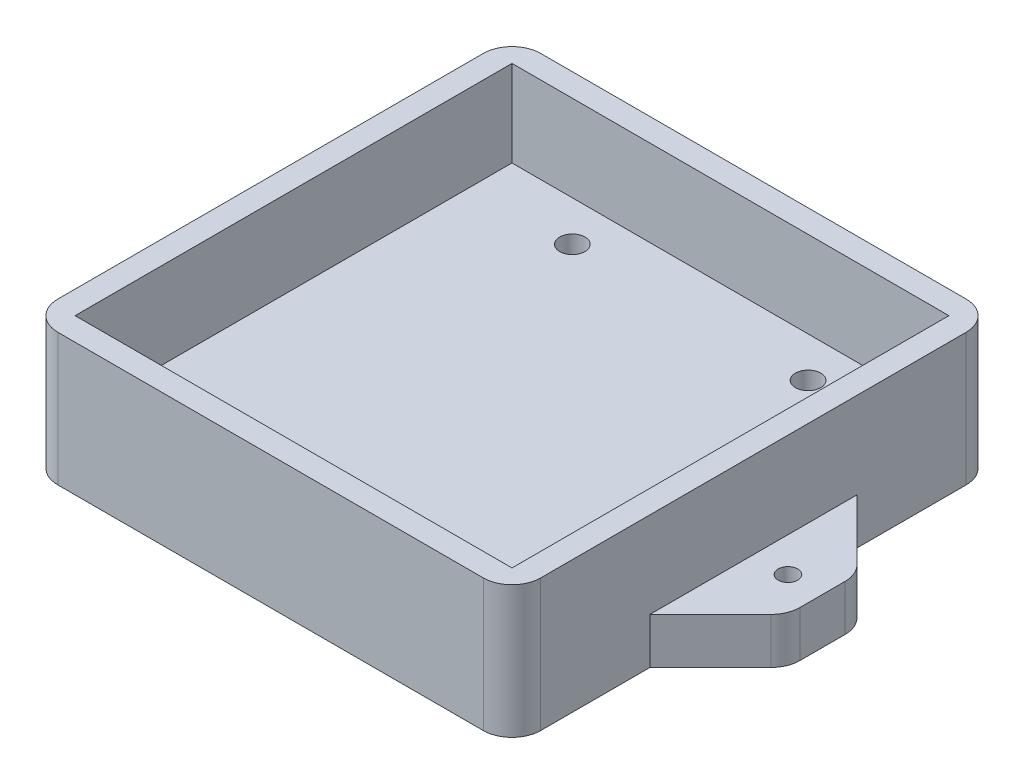
SolidWorks part; units mm, degrees
ref_plane "Front Plane" through (0, 0, 0) normal (0, 0, 1) x (1, 0, 0)
ref_plane "Top Plane" through (0, 0, 0) normal (0, 1, 0) x (1, 0, 0)
ref_plane "Right Plane" through (0, 0, 0) normal (1, 0, 0) x (0, 0, -1)
sketch "Sketch1" plane through (0, 0, 0) normal (0, 1, 0) x (1, 0, 0)
  line L0 (-42, 42) -> (-42, -42)
  line L1 (-20.5, 31) -> (20.5, 31) construction
  line L2 (-20.5, 31) -> (-20.5, -31) construction
  line L3 (-20.5, -31) -> (20.5, -31) construction
  line L4 (20.5, 31) -> (20.5, -31) construction
  line L5 (38, 38) -> (-38, 38)
  line L6 (38, 38) -> (38, -38)
  line L7 (38, -38) -> (-38, -38)
  line L8 (-38, 38) -> (-38, -38)
  line L9 (38, 38) -> (-38, -38) construction
  line L10 (38, -38) -> (-38, 38) construction
  line L11 (42, -42) -> (-42, -42)
  line L12 (42, 42) -> (42, -42)
  line L13 (42, 42) -> (-42, 42)
  line L14 (-54, 6) -> (-42, 18)
  line L15 (-42, 6) -> (-54, 6)
  line L16 (-42, 6) -> (-42, -6)
  line L17 (-42, -6) -> (-54, -6)
  line L18 (-54, 6) -> (-54, -6)
  line L19 (-54, -6) -> (-42, -18)
  line L20 (0, 0) -> (0, 31) construction
  line L21 (54, -6) -> (42, -18)
  line L22 (54, 6) -> (54, -6)
  line L23 (42, -6) -> (54, -6)
  line L24 (42, 6) -> (42, -6)
  line L25 (42, 6) -> (54, 6)
  line L26 (54, 6) -> (42, 18)
  circle A0 centre (-20.5, 31) radius 2.2
  circle A1 centre (20.5, 31) radius 2.2
  circle A2 centre (-20.5, -31) radius 2.2
  circle A3 centre (20.5, -31) radius 2.2
  circle A4 centre (-20.5, 31) radius 4.5
  circle A5 centre (20.5, 31) radius 4.5
  circle A6 centre (-20.5, -31) radius 4.5
  circle A7 centre (20.5, -31) radius 4.5
  circle A8 centre (-48, 0) radius 1.7
  circle A9 centre (48, 0) radius 1.7
  point P4 (0, 31)
  point P5 (-20.5, 0)
  point P11 (0, 0)
  point P28 (-48, 6)
  point P29 (-54, 0)
  point P33 (-42, 0)
  point P45 (42, 0)
  point P46 (54, 0)
  point P47 (48, 6)
  dimension "D3" = 4.4
  dimension "D4" = 4.4
  dimension "D5" = 4.4
  dimension "D6" = 4.4
  dimension "D10" = 9
  dimension "D11" = 9
  dimension "D12" = 9
  dimension "D13" = 9
  dimension "D15" = 3.4
  dimension "D1" = 62
  dimension "D2" = 41
  dimension "D7" = 76
  dimension "D8" = 76
  dimension "D14" = 12
  dimension "D16" = 45
  dimension "D17" = 45
  dimension "D9" = 4
extrude "Boss-Extrude1" add sketch "Sketch1" against normal blind 8 contours L12 L13 L0 L11 L8 L5 L6 L7 | L5 L8 L7 L6 A7 A6 A5 A4 | A6 A2 | A4 A0 | A5 A1 | A7 A3 | L15 L0 L14 | L15 L18 L17 L0 A8 | L17 L19 L0 | L25 L26 L12 | L25 L12 L23 L22 A9 | L23 L12 L21 region at (0, 0, -40.8121) region at (-46, 0, -10) region at (-42.1697, 0, 0) region at (46, 0, -10) region at (-46, 0, 10) region at (48, 0, -5.8303) region at (46, 0, 10) region at (0, 0, 0) region at (-24.8727, 0, -31) region at (16.1273, 0, -31) region at (-24.8727, 0, 31) region at (16.1273, 0, 31)
extrude "Boss-Extrude2" add sketch "Sketch1<3>" along normal blind 15 contours L12 L13 L0 L11 L8 L5 L6 L7 region at (0, 0, -40.8121)
sketch "Sketch1<3>" plane through (0, 0, 0) normal (0, 1, 0) x (1, 0, 0) same geometry as "Sketch1"
sketch "Sketch2" plane through (0, -8, 0) normal (0, -1, 0) x (1, 0, 0)
  circle A0 centre (-20.5, 31) radius 4.5 construction
  circle A1 centre (-20.5, 31) radius 4.5
  circle A2 centre (-20.5, -31) radius 4.5 construction
  circle A3 centre (20.5, -31) radius 4.5 construction
  circle A4 centre (20.5, 31) radius 4.5 construction
  circle A5 centre (-20.5, -31) radius 4.5
  circle A6 centre (20.5, -31) radius 4.5
  circle A7 centre (20.5, 31) radius 4.5
extrude "Cut-Extrude1" cut sketch "Sketch2" against normal blind 4.5
fillet "Fillet1" radius 5 8 edges at (42, 3.5, 42) (54, -4, 6) (54, -4, -6) (42, 3.5, -42) (-42, 3.5, -42) (-42, 3.5, 42) (-54, -4, 6) (-54, -4, -6)
